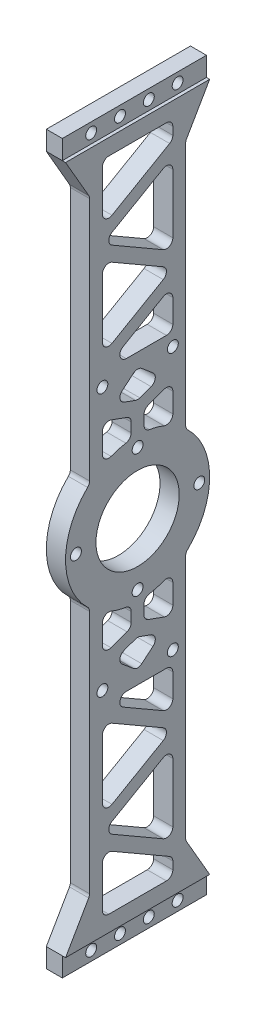
SolidWorks part; units mm, degrees
material "Сплав 2024"
ref_plane "Спереди" through (0, 0, 0) normal (0, 0, 1) x (1, 0, 0)
ref_plane "Сверху" through (0, 0, 0) normal (0, 1, 0) x (1, 0, 0)
ref_plane "Справа" through (0, 0, 0) normal (1, 0, 0) x (0, 0, -1)
sketch "Эскиз1" plane through (0, 0, 0) normal (0, 1, 0) x (1, 0, 0)
  line L1 (0, 0) -> (6, 0)
  line L2 (0, 0) -> (0, -30)
  line L3 (0, -30) -> (6, -30)
  line L4 (6, 0) -> (6, -30)
  dimension "D1" = 6
  dimension "D2" = 30
extrude "Бобышка-Вытянуть1" add sketch "Эскиз1" along normal blind 227
sketch "Эскиз2" plane through (0, 0, 0) normal (-1, 0, 0) x (0, 0, 1)
  line L0 (30, 113.5) -> (0, 113.5) construction
  line L1 (30, 227) -> (30, 0) construction
  line L2 (0, 227) -> (0, 0) construction
  line L3 (15, 227) -> (15, 0) construction
  line L4 (0, 227) -> (30, 227) construction
  line L5 (0, 0) -> (30, 0) construction
  circle A0 centre (15, 113.5) radius 22.5
  dimension "D1" = 45
extrude "Бобышка-Вытянуть2" add sketch "Эскиз2" against normal up to surface (6 mm away) up to face at (6, 113.5, 15)
sketch "Эскиз3" plane through (0, 0, 0) normal (-1, 0, 0) x (0, 0, 1)
  circle A0 centre (15, 113.5) radius 13
  dimension "D1" = 26
extrude "Вырез-Вытянуть1" cut sketch "Эскиз3" against normal through all
sketch "Эскиз4" plane through (6, 0, 0) normal (-1, 0, 0) x (0, 0, 1)
  line L0 (15, 136) -> (15, 91) construction
  line L1 (15, 227) -> (15, 0) construction
  line L2 (37.5, 113.5) -> (-7.5, 113.5) construction
  circle A0 centre (15, 113.5) radius 19.25 construction
  circle A1 centre (15, 113.5) radius 22.5 construction
  dimension "D1" = 38.5
hole_wizard "Отверстие с зазором M32" positions "Эскиз6" profile "Эскиз5" hole size "M3" standard "Ansi Metric" end condition up to next
sketch "Эскиз6" plane through (6, -25.0247, 7.2629) normal (-1, 0, 0) x (0, 0, 1)
  line L0 (7.7371, 161.0247) -> (7.7371, 116.0247) construction
  line L1 (30.2371, 138.5247) -> (-14.7629, 138.5247) construction
  circle A0 centre (7.7371, 138.5247) radius 19.25 construction
  point P0 (7.7371, 157.7747)
  point P6 (-11.5129, 138.5247)
  point P10 (7.7371, 119.2747)
  point P12 (26.9871, 138.5247)
sketch "Эскиз5" plane through (6, 132.75, 15) normal (0, 1, 0) x (0, 0, -1)
  line L0 (0, 0) -> (0, 6)
  line L1 (0, 6) -> (1.7, 6)
  line L2 (1.7, 6) -> (1.7, 0)
  line L5 (1.7, 0) -> (0, 0)
  line L11 (0, -6.35) -> (0, 107.95) construction
  dimension "Диаметр сквозного отверстия" = 3.4
  dimension "Глубина сквозного отверстия" = 6
sketch "Эскиз8" plane through (6, 0, 0) normal (1, 0, 0) x (0, 0, -1)
  line L0 (-15, 227) -> (-15, 0) construction
  line L1 (-30, 227) -> (0, 227) construction
  line L2 (-30, 0) -> (0, 0) construction
  line L3 (19.447, 113.5) -> (-49.447, 113.5) construction
  line L4 (0, 227) -> (0, 130.2705) construction
  line L5 (-26, 154.5) -> (-4, 154.5) construction
  line L6 (-26, 154.5) -> (-26, 72.5) construction
  line L7 (-26, 72.5) -> (-4, 72.5) construction
  line L8 (-4, 154.5) -> (-4, 72.5) construction
  line L9 (-30, 227) -> (-30, 130.2705) construction
  line L11 (-26, 154.5) -> (-4, 72.5) construction
  line L12 (-4, 154.5) -> (-26, 72.5) construction
  point P8 (-15, 113.5)
  point P9 (-15, 113.5)
  dimension "D1" = 4
  dimension "D2" = 82
  dimension "D4" = 4
hole_wizard "Отверстие с зазором M33" positions "Эскиз10" profile "Эскиз9" hole size "M3" standard "Ansi Metric" end condition through all
sketch "Эскиз10" plane through (6, 0, 0) normal (1, 0, 0) x (0, 0, -1)
  point P0 (-26, 154.5)
  point P3 (-4, 154.5)
  point P6 (-4, 72.5)
  point P9 (-26, 72.5)
sketch "Эскиз9" plane through (6, 154.5, 26) normal (0, 1, 0) x (0, 0, -1)
  line L0 (0, 0) -> (0, 6)
  line L1 (0, 6) -> (1.7, 6)
  line L2 (1.7, 6) -> (1.7, 0)
  line L5 (1.7, 0) -> (0, 0)
  line L11 (0, -6.35) -> (0, 107.95) construction
  dimension "Диаметр сквозного отверстия" = 3.4
  dimension "Глубина сквозного отверстия" = 6
sketch "Эскиз11" plane through (6, 0, 0) normal (1, 0, 0) x (0, 0, -1)
  line L0 (-15, 227) -> (-15, 0) construction
  line L1 (-30, 227) -> (0, 227) construction
  line L2 (-30, 0) -> (0, 0) construction
  line L3 (-37.5, 221) -> (-30, 208.0096)
  line L4 (-37.5, 221) -> (7.5, 221) construction
  line L5 (-37.5, 221) -> (-37.5, 227)
  line L6 (-37.5, 227) -> (7.5, 227)
  line L7 (7.5, 221) -> (7.5, 227)
  line L8 (-37.5, 221) -> (7.5, 227) construction
  line L9 (-37.5, 227) -> (7.5, 221) construction
  line L10 (-30, 227) -> (-30, 130.2705) construction
  line L11 (-30, 208.0096) -> (0, 208.0096)
  line L12 (0, 227) -> (0, 130.2705) construction
  line L13 (0, 208.0096) -> (7.5, 221)
  line L14 (-37.5, 224) -> (7.5, 224) construction
  line L15 (-28.5, 227) -> (-28.5, 221) construction
  line L16 (-19.5, 227) -> (-19.5, 221) construction
  line L17 (-10.5, 227) -> (-10.5, 221) construction
  line L18 (-1.5, 227) -> (-1.5, 221) construction
  line L19 (-15, 113.5) -> (-5.455, 113.5) construction
  line L20 (-1.5, 0) -> (-1.5, 6) construction
  line L21 (-10.5, 0) -> (-10.5, 6) construction
  line L22 (-19.5, 0) -> (-19.5, 6) construction
  line L23 (-28.5, 0) -> (-28.5, 6) construction
  line L24 (-37.5, 3) -> (7.5, 3) construction
  line L25 (-37.5, 0) -> (7.5, 6) construction
  line L26 (-37.5, 6) -> (7.5, 0) construction
  line L27 (-37.5, 6) -> (7.5, 6) construction
  line L28 (0, 18.9904) -> (7.5, 6)
  line L29 (-30, 18.9904) -> (0, 18.9904)
  line L30 (7.5, 6) -> (7.5, 0)
  line L31 (-37.5, 0) -> (7.5, 0)
  line L32 (-37.5, 6) -> (-37.5, 0)
  line L33 (-37.5, 6) -> (-30, 18.9904)
  point P6 (-15, 224)
  point P45 (-15, 3)
  dimension "D1" = 6
  dimension "D2" = 45
  dimension "D3" = 120
  dimension "D4" = 9
  dimension "D5" = 9
  dimension "D6" = 9
  dimension "D7" = 9
extrude "Бобышка-Вытянуть3" add sketch "Эскиз11" against normal up to surface (6 mm away) up to face at (0, 154.5, 24.3)
hole_wizard "Отверстие с зазором M31" positions "Эскиз13" profile "Эскиз12" hole size "M3" standard "Ansi Metric" end condition through all
sketch "Эскиз13" plane through (6, 0, 0) normal (1, 0, 0) x (0, 0, -1)
  line L0 (-28.5, 227) -> (-28.5, 221) construction
  line L1 (-19.5, 227) -> (-19.5, 221) construction
  line L2 (-10.5, 227) -> (-10.5, 221) construction
  line L3 (-1.5, 227) -> (-1.5, 221) construction
  line L4 (-28.5, 0) -> (-28.5, 6) construction
  line L5 (-19.5, 0) -> (-19.5, 6) construction
  line L6 (-10.5, 0) -> (-10.5, 6) construction
  line L7 (-1.5, 0) -> (-1.5, 6) construction
  point P0 (-28.5, 224)
  point P4 (-19.5, 224)
  point P8 (-10.5, 224)
  point P12 (-1.5, 224)
  point P16 (-28.5, 3)
  point P20 (-19.5, 3)
  point P24 (-10.5, 3)
  point P28 (-1.5, 3)
sketch "Эскиз12" plane through (6, 224, 28.5) normal (0, 1, 0) x (0, 0, -1)
  line L0 (0, 0) -> (0, 6)
  line L1 (0, 6) -> (1.7, 6)
  line L2 (1.7, 6) -> (1.7, 0)
  line L5 (1.7, 0) -> (0, 0)
  line L11 (0, -6.35) -> (0, 107.95) construction
  dimension "Диаметр сквозного отверстия" = 3.4
  dimension "Глубина сквозного отверстия" = 6
sketch "Эскиз14" plane through (6, 0, 0) normal (1, 0, 0) x (0, 0, -1)
  line L1 (-37.5, 227) -> (7.5, 227)
  line L2 (-37.5, 227) -> (-37.5, 221)
  line L3 (-37.5, 221) -> (7.5, 221)
  line L4 (7.5, 227) -> (7.5, 221)
  line L5 (-37.5, 0) -> (7.5, 0)
  line L6 (-37.5, 0) -> (-37.5, 6)
  line L7 (-37.5, 6) -> (7.5, 6)
  line L8 (7.5, 0) -> (7.5, 6)
extrude "Вырез-Вытянуть2" cut sketch "Эскиз14" against normal blind 1
sketch "Эскиз15" plane through (0, 0, 0) normal (-1, 0, 0) x (0, 0, 1)
  line L0 (4, 0) -> (4, 227) construction
  line L1 (-7.5, 0) -> (37.5, 0) construction
  line L2 (-7.5, 227) -> (37.5, 227) construction
  line L3 (26, 227) -> (26, 0) construction
  line L4 (0, 96.7295) -> (0, 18.9904) construction
  line L5 (30, 96.7295) -> (30, 18.9904) construction
  line L6 (13, 91.0891) -> (13, 85.0058)
  line L7 (17, 91.0891) -> (17, 85.0058)
  line L8 (15, 227) -> (15, 0) construction
  line L9 (17, 85.0058) -> (26, 81.7301)
  line L10 (13, 85.0058) -> (4, 81.7301)
  line L11 (7.5382, 78.7612) -> (15, 81.4771)
  line L12 (15, 81.4771) -> (22.4618, 78.7612)
  line L13 (22.4618, 78.7612) -> (15, 72.5)
  line L14 (15, 72.5) -> (7.5382, 78.7612)
  line L15 (0, 78.7612) -> (30, 78.7612) construction
  line L16 (4, 81.7301) -> (4, 93.8722)
  line L17 (26, 81.7301) -> (26, 93.8722)
  line L18 (4, 72.5) -> (26, 72.5) construction
  line L19 (4, 81.7301) -> (15, 72.5) construction
  line L20 (26, 81.7301) -> (15, 72.5) construction
  line L21 (-7.5, 6) -> (37.5, 6) construction
  line L22 (-4.6132, 11) -> (34.6132, 11) construction
  line L23 (0, 18.9904) -> (-7.5, 6) construction
  line L24 (37.5, 6) -> (30, 18.9904) construction
  line L25 (4, 68.5) -> (26, 68.5)
  line L26 (26, 68.5) -> (4, 55.7983)
  line L27 (4, 55.7983) -> (4, 68.5)
  line L28 (4, 51.1795) -> (26, 63.8812)
  line L29 (26, 63.8812) -> (26, 38.4778)
  line L30 (26, 38.4778) -> (4, 51.1795)
  line L31 (4, 46.5607) -> (26, 33.859)
  line L32 (26, 33.859) -> (4, 21.1573)
  line L33 (4, 21.1573) -> (4, 46.5607)
  line L34 (4, 11) -> (4, 16.5385)
  line L35 (26, 29.2402) -> (26, 11)
  line L36 (26, 11) -> (4, 11)
  line L37 (4, 16.5385) -> (26, 29.2402)
  line L38 (15, 113.5) -> (28, 113.5) construction
  line L39 (4, 171.2017) -> (4, 158.5)
  line L40 (26, 145.2699) -> (26, 133.1278)
  line L41 (4, 145.2699) -> (4, 133.1278)
  line L42 (13, 141.9942) -> (4, 145.2699)
  line L43 (13, 135.9109) -> (13, 141.9942)
  line L44 (17, 135.9109) -> (17, 141.9942)
  line L45 (17, 141.9942) -> (26, 145.2699)
  line L46 (15, 145.5229) -> (22.4618, 148.2388)
  line L47 (7.5382, 148.2388) -> (15, 145.5229)
  line L48 (15, 154.5) -> (7.5382, 148.2388)
  line L49 (22.4618, 148.2388) -> (15, 154.5)
  line L50 (4, 158.5) -> (26, 158.5)
  line L51 (26, 158.5) -> (4, 171.2017)
  line L52 (4, 175.8205) -> (26, 163.1188)
  line L53 (26, 163.1188) -> (26, 188.5222)
  line L54 (26, 188.5222) -> (4, 175.8205)
  line L55 (4, 180.4393) -> (26, 193.141)
  line L56 (4, 205.8427) -> (4, 180.4393)
  line L57 (26, 193.141) -> (4, 205.8427)
  line L58 (4, 216) -> (4, 210.4615)
  line L59 (4, 210.4615) -> (26, 197.7598)
  line L60 (26, 197.7598) -> (26, 216)
  line L61 (26, 216) -> (4, 216)
  circle A0 centre (15, 113.5) radius 22.5 construction
  arc A1 (4, 93.8722) -> (13, 91.0891) centre (15, 113.5) ccw
  circle A2 centre (15, 113.5) radius 13 construction
  arc A3 (17, 91.0891) -> (26, 93.8722) centre (15, 113.5) ccw
  arc A4 (17, 135.9109) -> (26, 133.1278) centre (15, 113.5) cw
  arc A5 (4, 133.1278) -> (13, 135.9109) centre (15, 113.5) cw
  point P12 (4, 93.8722)
  point P13 (26, 93.8722)
  dimension "D3" = 4
  dimension "D1" = 4
  dimension "D2" = 4
  dimension "D4" = 2
  dimension "D5" = 110
  dimension "D6" = 4
  dimension "D7" = 100
  dimension "D8" = 5
  dimension "D9" = 30
  dimension "D10" = 60
  dimension "D11" = 60
  dimension "D12" = 4
  dimension "D13" = 4
  dimension "D14" = 4
  dimension "D15" = 4
extrude "Вырез-Вытянуть3" cut sketch "Эскиз15" against normal up to next
fillet "Скругление1" radius 2 58 edges at (3, 171.2017, 4) (3, 11, 26) (3, 29.2402, 26) (3, 11, 4) (3, 16.5385, 4) (3, 21.1573, 4) (3, 46.5607, 4) (3, 33.859, 26) (3, 38.4778, 26) (3, 63.8812, 26) (3, 51.1795, 4) (3, 55.7983, 4) (3, 68.5, 26) (3, 68.5, 4) (3, 85.0058, 17) (3, 93.8722, 26) (3, 78.7612, 22.4618) (3, 91.0891, 13) (3, 72.5, 15) (3, 81.7301, 26) (3, 85.0058, 13) (3, 81.4771, 15) (3, 91.0891, 17) (3, 78.7612, 7.5382) (3, 81.7301, 4) (3, 93.8722, 4) (3, 148.2388, 7.5382) (3, 148.2388, 22.4618) (3, 141.9942, 13) (3, 145.2699, 26) (3, 133.1278, 26) (3, 135.9109, 13) (3, 145.5229, 15) (3, 135.9109, 17) (3, 133.1278, 4) (3, 141.9942, 17) (3, 154.5, 15) (3, 145.2699, 4) (3, 188.5222, 26) (3, 175.8205, 4) (3, 163.1188, 26) (3, 158.5, 26) (3, 193.141, 26) (3, 158.5, 4) (3, 180.4393, 4) (3, 205.8427, 4) (3, 216, 26) (3, 197.7598, 26) (3, 210.4615, 4) (3, 216, 4) (3, 208.0096, 30) (3, 208.0096, 0) (3, 130.2705, 0) (3, 96.7295, 0) (3, 96.7295, 30) (3, 130.2705, 30) (3, 18.9904, 30) (3, 18.9904, 0)
equation "\"D4@Эскиз11\"=\"D2@Эскиз11\"/5"
equation "\"D5@Эскиз11\"=\"D4@Эскиз11\""
equation "\"D6@Эскиз11\"=\"D4@Эскиз11\""
equation "\"D7@Эскиз11\"=\"D4@Эскиз11\""
